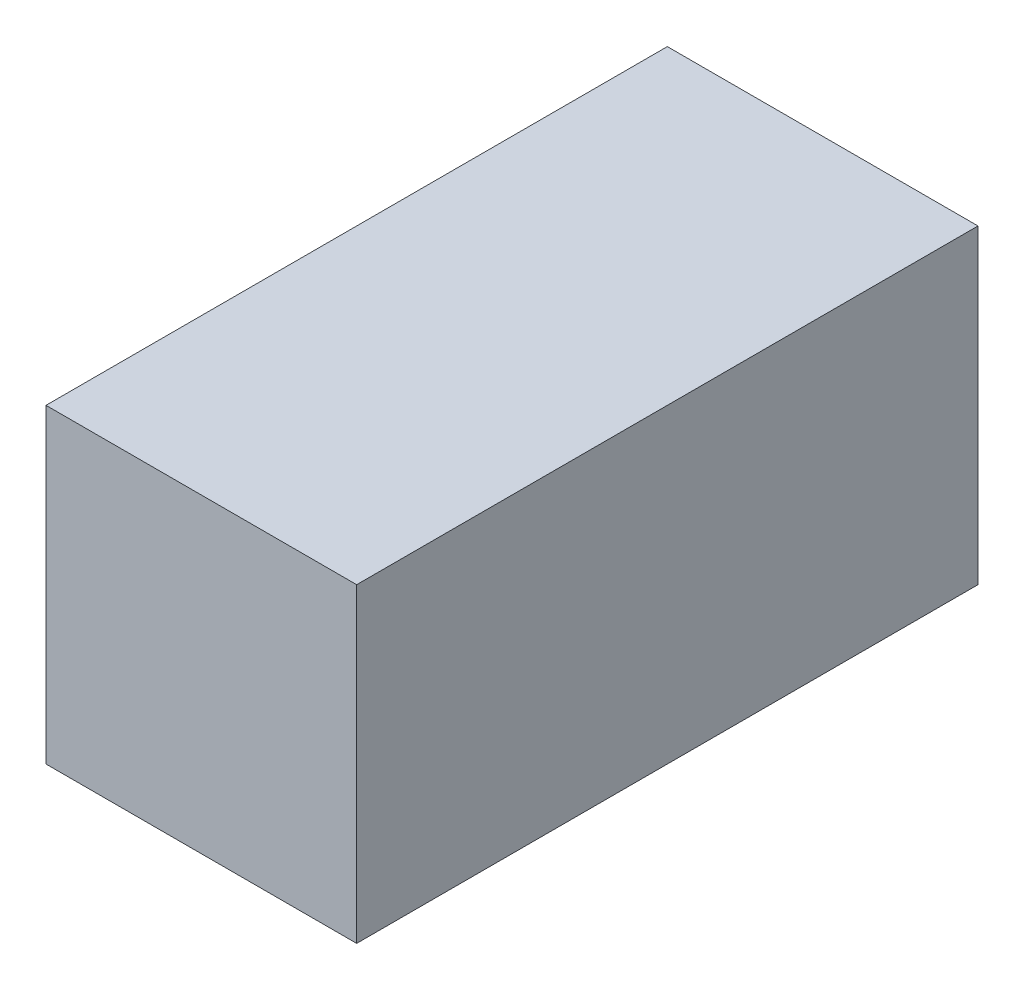
SolidWorks part; units mm, degrees
ref_plane "Front Plane" through (0, 0, 0) normal (0, 0, 1) x (1, 0, 0)
ref_plane "Top Plane" through (0, 0, 0) normal (0, 1, 0) x (1, 0, 0)
ref_plane "Right Plane" through (0, 0, 0) normal (1, 0, 0) x (0, 0, -1)
sketch "Sketch1" plane through (0, 0, 0) normal (0, 0, 1) x (1, 0, 0)
  line L1 (0, 0) -> (76.2, 0)
  line L2 (0, 0) -> (0, 76.2)
  line L3 (0, 76.2) -> (76.2, 76.2)
  line L4 (76.2, 0) -> (76.2, 76.2)
  dimension "D1" = 76.2
  dimension "D2" = 76.2
extrude "Boss-Extrude1" add sketch "Sketch1" along normal blind 152.4
